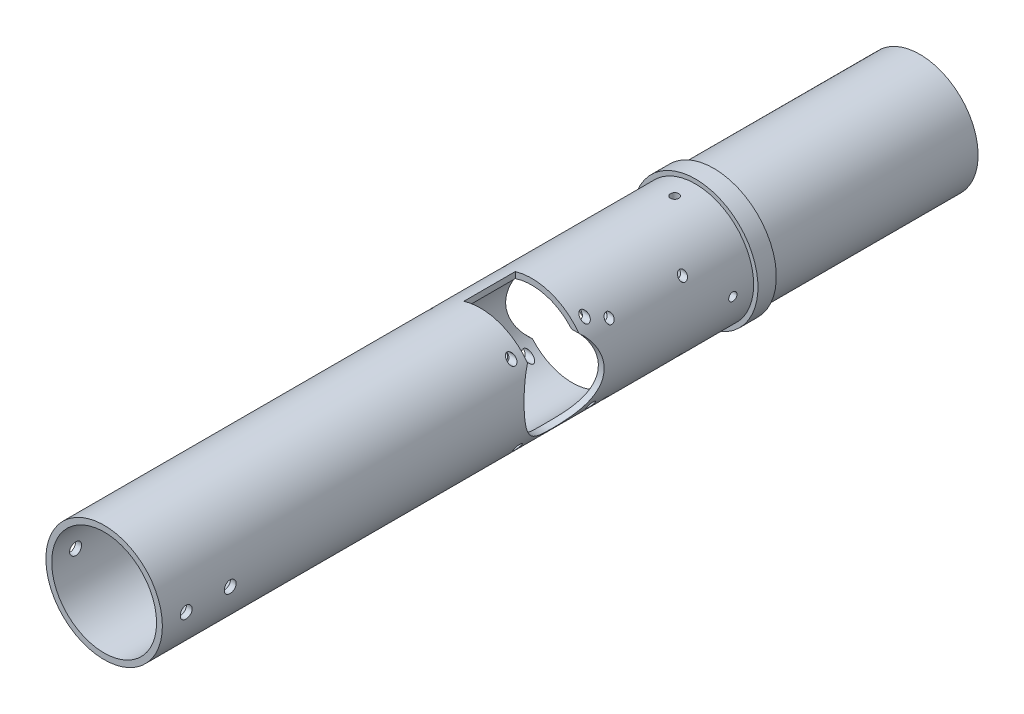
SolidWorks part; units mm, degrees
material "6061 Alloy"
ref_plane "Front Plane" through (0, 0, 0) normal (0, 0, 1) x (1, 0, 0)
ref_plane "Top Plane" through (0, 0, 0) normal (0, 1, 0) x (1, 0, 0)
ref_plane "Right Plane" through (0, 0, 0) normal (1, 0, 0) x (0, 0, -1)
sketch "Sketch1" plane through (0, 0, 0) normal (0, 0, 1) x (1, 0, 0)
  circle A0 centre (0, 0) radius 31.75
  circle A1 centre (0, 0) radius 28.575
  dimension "D1" = 63.5
  dimension "D2" = 57.15
extrude "Boss-Extrude1" add sketch "Sketch1" along normal blind 125 and the other way blind 250 contours A1 | A0
sketch "Sketch2" plane through (0, 0, 0) normal (1, 0, 0) x (0, 0, -1)
  circle A2 centre (73.488, -2) radius 21.75
  dimension "D1" = 43.5
  dimension "D2" = 73.488
  dimension "D3" = 2
extrude "Cut-Extrude1" cut sketch "Sketch2" against normal through all
sketch "Sketch3" plane through (0, 0, 0) normal (1, 0, 0) x (0, 0, -1)
  circle A1 centre (23.45, 2) radius 21.75
  dimension "D1" = 23.45
  dimension "D2" = 43.5
  dimension "D3" = 2
extrude "Cut-Extrude2" cut sketch "Sketch3" along normal through all
sketch "Sketch5" plane through (0, 0, 0) normal (1, 0, 0) x (0, 0, -1)
  line L1 (87.488, -12.75) -> (59.488, -12.75)
  line L2 (87.488, -12.75) -> (87.488, -34.75)
  line L3 (87.488, -34.75) -> (59.488, -34.75)
  line L4 (59.488, -12.75) -> (59.488, -34.75)
  line L5 (87.488, -12.75) -> (59.488, -34.75) construction
  line L6 (87.488, -34.75) -> (59.488, -12.75) construction
  circle A0 centre (73.488, -2) radius 21.75 construction
  circle A1 centre (73.488, -2) radius 21.75 construction
  circle A2 centre (73.488, -2) radius 21.75 construction
  point P0 (73.488, -23.75)
  dimension "D1" = 28
  dimension "D2" = 22
extrude "Cut-Extrude4" cut sketch "Sketch5" against normal through all from offset 9
sketch "Sketch6" plane through (0, 0, 0) normal (1, 0, 0) x (0, 0, -1)
  line L1 (9.45, 34.75) -> (37.45, 34.75)
  line L2 (9.45, 34.75) -> (9.45, 12.75)
  line L3 (9.45, 12.75) -> (37.45, 12.75)
  line L4 (37.45, 34.75) -> (37.45, 12.75)
  line L5 (9.45, 34.75) -> (37.45, 12.75) construction
  line L6 (9.45, 12.75) -> (37.45, 34.75) construction
  circle A0 centre (23.45, 2) radius 21.75 construction
  circle A1 centre (23.45, 2) radius 21.75 construction
  circle A2 centre (23.45, 2) radius 21.75 construction
  point P0 (23.45, 23.75)
  dimension "D1" = 28
  dimension "D2" = 22
extrude "Cut-Extrude5" cut sketch "Sketch6" along normal through all from offset 9 offset against normal yes
sketch "Sketch10" plane through (0, 0, 0) normal (1, 0, 0) x (0, 0, -1)
  line L1 (113.488, 38) -> (33.488, 38)
  line L2 (113.488, 38) -> (113.488, -42)
  line L3 (113.488, -42) -> (33.488, -42)
  line L4 (33.488, 38) -> (33.488, -42)
  line L5 (113.488, 38) -> (33.488, -42) construction
  line L6 (113.488, -42) -> (33.488, 38) construction
  point P0 (73.488, -2)
  dimension "D1" = 80
  dimension "D2" = 80
sketch "Sketch11" plane through (0, 0, 0) normal (1, 0, 0) x (0, 0, -1)
  line L0 (113.488, 38) -> (33.488, -42) construction
  line L1 (113.488, -42) -> (33.488, 38) construction
  line L2 (51.738, -2) -> (95.238, -2) construction
  line L3 (53.488, 18) -> (53.488, -22) construction
  circle A0 centre (93.488, 18) radius 2
  circle A1 centre (53.488, 18) radius 2
  circle A2 centre (53.488, -22) radius 2
  circle A3 centre (93.488, -22) radius 2
  arc A4 (87.488, -18.6452) -> (59.488, -18.6452) centre (73.488, -2) ccw construction
  arc A5 (87.488, -18.6452) -> (59.488, -18.6452) centre (73.488, -2) ccw construction
  point P18 (53.488, -2)
  dimension "D5" = 4
  dimension "D1" = 40
extrude "Cut-Extrude8" cut sketch "Sketch11" against normal through all both and the other way through all
sketch "Sketch12" plane through (0, 0, 0) normal (1, 0, 0) x (0, 0, -1)
  line L0 (-125, 31.75) -> (-125, -31.75) construction
  circle A0 centre (-112, 0) radius 3.25
  circle A1 centre (-88, 0) radius 3.25
  dimension "D2" = 6.5
  dimension "D3" = 24
  dimension "D4" = 13
extrude "Cut-Extrude10" cut sketch "Sketch12" against normal through all both and the other way through all
sketch "Sketch13" plane through (0, 0, 0) normal (0, 1, 0) x (1, 0, 0)
  line L0 (0, -34.925) -> (0, 34.925) construction
  line L1 (28.575, 250) -> (-28.575, 250) construction
  line L2 (0, 250) -> (0, -125) construction
  circle A0 centre (0, 238) radius 2.25 construction
  circle A1 centre (0, 205.9) radius 2.25 construction
  dimension "D2" = 4.5
  dimension "D3" = 32.1
  dimension "D1" = 12
sketch "Sketch14" plane through (0, 0, 0) normal (1, 0, 0) x (0, 0, -1)
  line L0 (3.45, -18) -> (3.45, 22) construction
  line L1 (-1.55, 27) -> (48.45, 27) construction
  line L2 (-1.55, 27) -> (-1.55, -23) construction
  line L3 (-1.55, -23) -> (48.45, -23) construction
  line L4 (48.45, 27) -> (48.45, -23) construction
  line L5 (-1.55, 27) -> (48.45, -23) construction
  line L6 (-1.55, -23) -> (48.45, 27) construction
  circle A0 centre (3.45, 22) radius 2
  circle A1 centre (43.45, 22) radius 2
  circle A2 centre (43.45, -18) radius 2
  circle A3 centre (3.45, -18) radius 2
  point P0 (23.45, 2)
  point P14 (3.45, 2)
  dimension "D5" = 4
  dimension "D1" = 40
  dimension "D2" = 50
sketch "Sketch15" plane through (0, 0, 0) normal (1, 0, 0) x (0, 0, -1)
  circle A0 centre (3.45, 22) radius 2
  circle A1 centre (43.45, 22) radius 2
  circle A2 centre (43.45, -18) radius 2
  circle A3 centre (3.45, -18) radius 2
  dimension "D1" = 4
extrude "Cut-Extrude12" cut sketch "Sketch15" against normal through all and the other way through all
hole_wizard "M4 Clearance Hole1" positions "Sketch18" profile "Sketch19" hole size "M4" standard "ANSI Metric"
sketch "Sketch18" plane through (0, 0, 0) normal (1, 0, 0) x (0, 0, -1)
  circle A0 centre (3.45, 22) radius 2 construction
  circle A1 centre (43.45, 22) radius 2 construction
  circle A2 centre (3.45, -18) radius 2 construction
  circle A3 centre (43.45, -18) radius 2 construction
  point P0 (3.45, 22)
  point P2 (43.45, 22)
  point P4 (3.45, -18)
  point P6 (43.45, -18)
  point P20 (93.488, 18)
  point P23 (53.488, 18)
  point P26 (93.488, -22)
  point P29 (53.488, -22)
sketch "Sketch19" plane through (0, 22, -3.45) normal (0, 1, 0) x (0, 0, 1)
  line L0 (0, 0) -> (0, 31.75)
  line L1 (0, 31.75) -> (2.25, 31.75)
  line L2 (2.25, 31.75) -> (2.25, 0)
  line L5 (2.25, 0) -> (0, 0)
  line L11 (0, -6.35) -> (0, 107.95) construction
  dimension "Thru Hole Dia." = 4.5
  dimension "Thru Hole Depth" = 31.75
mirror "Mirror1" about plane through (0, 0, 0) normal (1, 0, 0) of "M4 Clearance Hole1"
sketch "Sketch21" plane through (0, 0, -250) normal (0, 0, -1) x (-1, 0, 0)
  circle A0 centre (0, 0) radius 30
  dimension "D1" = 60
extrude "Cut-Extrude14" cut sketch "Sketch21" against normal blind 7
sketch "Sketch22" plane through (0, 0, 0) normal (1, 0, 0) x (0, 0, -1)
  line L0 (250, -31.75) -> (250, 31.75) construction
  line L1 (250, -31.75) -> (250, 31.75) construction
  circle A0 centre (221.65, 0) radius 2.25 construction
  circle A1 centre (131.65, 0) radius 2.25 construction
  circle A2 centre (115.3, 0) radius 2.25
  circle A4 centre (238, 0) radius 2.25 construction
  point P14 (250, 0)
  dimension "D1" = 134.7
  dimension "D4" = 12
  dimension "D5" = 4.5
  dimension "D2" = 118.35
  dimension "D3" = 28.35
extrude "Cut-Extrude15" cut sketch "Sketch22" along normal through all
sketch "Sketch23" plane through (0, 0, -243) normal (0, 0, -1) x (-1, 0, 0)
  circle A0 centre (0, 0) radius 28.575 construction
  circle A1 centre (0, 0) radius 30
  circle A2 centre (0, 0) radius 30
  circle A3 centre (0, 0) radius 28.575
  dimension "D1" = 0
extrude "Boss-Extrude2" add sketch "Sketch23" along normal up to surface (7 mm away) up to face at (-30, 0, -250)
pattern_circular "CirPattern2" count 4 over 360 about axis through (0, 0, -250) along (0, 0, 1) of "Cut-Extrude15"
ref_plane "Plane1" through (0, 0, 75) normal (0, 0, 1) x (1, 0, 0)
split "Split1" trim tools "Plane1" bodies to split 123 resulting bodies 125 126
move or copy body "Body-Move/Copy1" bodies to move or copy 125 copy no translate (0, 0, 70.65) parameters "D1"=0, "D2"=0, "D3"=70.65
sketch "Sketch24" plane through (0, 0, 75) normal (0, 0, 1) x (1, 0, 0)
  circle A0 centre (0, 0) radius 28.575 construction
  circle A1 centre (0, 0) radius 31.75
  circle A2 centre (0, 0) radius 31.75
  circle A3 centre (0, 0) radius 28.575
  dimension "D1" = 0
extrude "Boss-Extrude3" add sketch "Sketch24" along normal up to surface (70.65 mm away) up to face at (31.75, 0, 145.65)
sketch "Sketch25" plane through (0, 0, -250) normal (0, 0, -1) x (-1, 0, 0)
  circle A0 centre (0, 0) radius 31.75 construction
  circle A1 centre (0, 0) radius 31.75
extrude "Cut-Extrude16" cut sketch "Sketch25" against normal blind 1
ref_plane "Plane2" through (0, 0, -126.65) normal (0, 0, -1) x (-1, 0, 0)
sketch "Sketch26" plane through (0, 0, -126.65) normal (0, 0, -1) x (-1, 0, 0)
  circle A0 centre (0, 0) radius 34.1
  circle A1 centre (0, 0) radius 31.75 construction
  circle A2 centre (0, 0) radius 31.75
  dimension "D1" = 68.2
extrude "Boss-Extrude4" add sketch "Sketch26" along normal blind 10
sketch "Sketch29" plane through (0, 0, -249) normal (0, 0, -1) x (-1, 0, 0)
  circle A0 centre (0, 0) radius 21
  circle A1 centre (0, 0) radius 28.575 construction
  circle A2 centre (0, 0) radius 28.575
  dimension "D1" = 42
extrude "Boss-Extrude5" add sketch "Sketch29" against normal blind 10
sketch "Sketch27" plane through (0, 0, -249) normal (0, 0, -1) x (-1, 0, 0)
  line L0 (2.25, 0) -> (-2.25, 0) construction
  circle A0 centre (0, 0) radius 24.75 construction
  point P4 (0, 24.75)
  dimension "D1" = 49.5
hole_wizard "M4x0.7 Tapped Hole1" positions "Sketch27" profile "Sketch31" tap size "M4x0.7" standard "ANSI Metric" end condition through all
sketch "Sketch31" plane through (0, 24.75, -249) normal (1, 0, 0) x (0, 1, 0)
  line L0 (0, 0) -> (0, 444.65)
  line L1 (0, 444.65) -> (1.65, 444.65)
  line L2 (1.65, 444.65) -> (1.65, 0)
  line L5 (1.65, 0) -> (0, 0)
  line L11 (0, -6.35) -> (0, 107.95) construction
  dimension "Thru Tap Drill Dia." = 3.3
  dimension "Thru Tap Drill Depth" = 444.65
cosmetic thread "Hole Thread1" parameters "D2"=4
pattern_circular "CirPattern3" count 8 over 360 about axis through (0, 0, 0) along (0, 0, 1) of "M4x0.7 Tapped Hole1"
cosmetic thread "Hole Thread2" parameters "D2"=4
cosmetic thread "Hole Thread3" parameters "D2"=4
cosmetic thread "Hole Thread4" parameters "D2"=4
cosmetic thread "Hole Thread5" parameters "D2"=4
cosmetic thread "Hole Thread6" parameters "D2"=4
cosmetic thread "Hole Thread7" parameters "D2"=4
cosmetic thread "Hole Thread8" parameters "D2"=4
